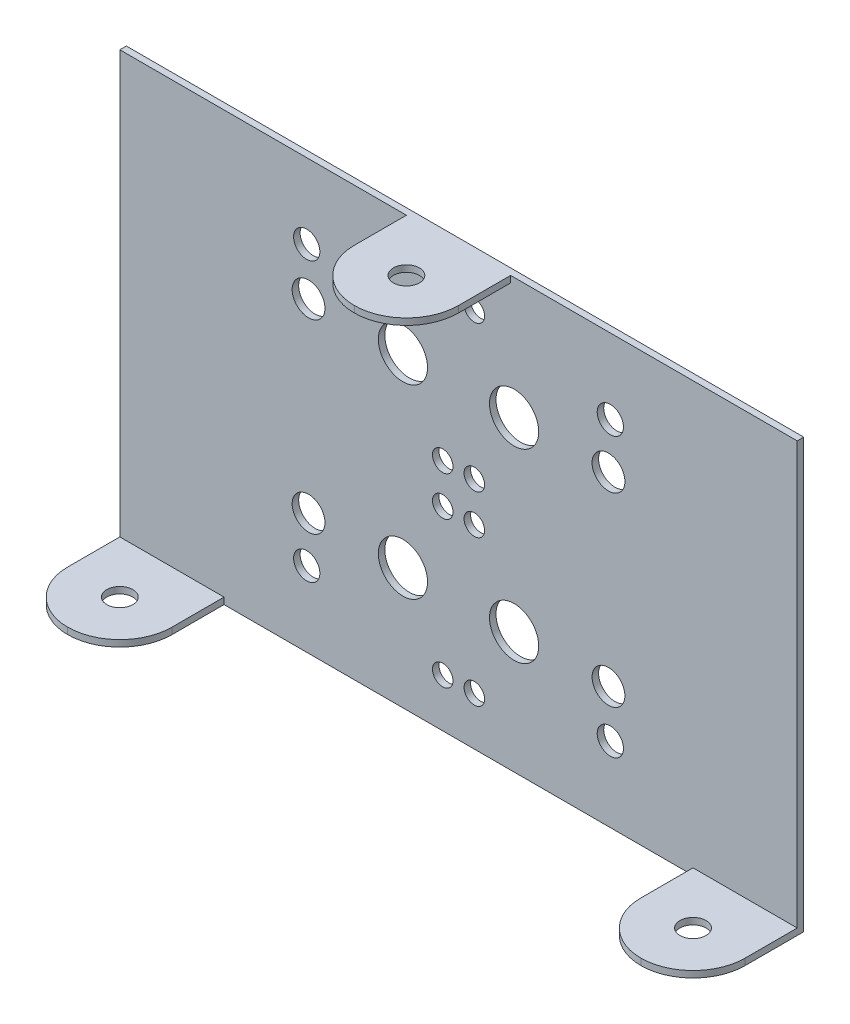
SolidWorks part; units mm, degrees
ref_plane "Front Plane" through (0, 0, 0) normal (0, 0, 1) x (1, 0, 0)
ref_plane "Top Plane" through (0, 0, 0) normal (0, 1, 0) x (1, 0, 0)
ref_plane "Right Plane" through (0, 0, 0) normal (1, 0, 0) x (0, 0, -1)
sketch "Sketch1" plane through (0, 0, 0) normal (0, 1, 0) x (1, 0, 0)
  line L0 (0, 0) -> (-69.85, 0)
  line L1 (-69.85, 0) -> (-69.85, 12.7)
  line L2 (-69.85, 12.7) -> (0, 12.7)
  line L3 (0, 12.7) -> (0, 0)
  line L4 (-69.85, 6.35) -> (-63.5, 6.35)
  line L5 (-34.925, 0) -> (-34.925, 12.7)
  line L6 (-63.5, 6.35) -> (-57.15, 6.35)
  line L7 (-57.15, 6.35) -> (-57.15, 12.7)
  line L8 (-57.15, 6.35) -> (-57.15, 0)
  line L9 (-12.7, 6.35) -> (-12.7, 0)
  line L10 (-12.7, 6.35) -> (-12.7, 12.7)
  line L11 (-6.35, 6.35) -> (-12.7, 6.35)
  circle A0 centre (-63.5, 6.35) radius 1.5875
  circle A1 centre (-6.35, 6.35) radius 1.5875
  dimension "D4" = 3.175
  dimension "D1" = 69.85
  dimension "D2" = 12.7
  dimension "D3" = 6.35
  dimension "D5" = 34.925
  dimension "D6" = 34.925
  dimension "D7" = 12.7
  dimension "D8" = 12.7
extrude "Boss-Extrude1" add sketch "Sketch1" along normal blind 1.5875 contours A0 L4 L1 L0 L8 L6 | A0 L6 L7 L2 L1 L4 | A1 L9 L0 L3 L2 L10 region at (-6.35, 0, -0.1796) region at (-63.5, 0, -3.0459) region at (-63.5, 0, -9.6541)
sketch "Sketch2" plane through (0, 0, -12.7) normal (0, 0, -1) x (-1, 0, 0)
  line L1 (0, 0) -> (69.85, 0)
  line L2 (0, 0) -> (0, 53)
  line L3 (0, 53) -> (69.85, 53)
  line L4 (69.85, 0) -> (69.85, 53)
  dimension "D1" = 69.85
  dimension "D2" = 53
extrude "Boss-Extrude2" add sketch "Sketch2" along normal blind 1.5875
sketch "Sketch3" plane through (0, 0, -14.2875) normal (0, 0, -1) x (-1, 0, 0)
  line L0 (-27.8972, 15.9448) -> (-27.8972, 27.4448)
  line L1 (-27.8972, 38.6448) -> (-27.8972, 27.4448)
  line L2 (-39.2472, 38.6448) -> (-16.5472, 38.6448)
  line L3 (-39.2472, 38.6448) -> (-39.2472, -3.3552)
  line L4 (-39.2472, -3.3552) -> (-16.5472, -3.3552)
  line L5 (-16.5472, 38.6448) -> (-16.5472, -3.3552)
  line L6 (-36.7972, 36.1448) -> (-18.9972, 36.1448)
  line L7 (-39.2472, 38.6448) -> (-36.7972, 38.6448)
  line L8 (-39.2472, 38.6448) -> (-39.2472, 36.1448)
  line L9 (-39.2472, 36.1448) -> (-36.7972, 36.1448)
  line L10 (-36.7972, 38.6448) -> (-36.7972, 36.1448)
  circle A0 centre (-27.8972, 15.9448) radius 2
  circle A1 centre (-27.8972, 27.4448) radius 3
  circle A2 centre (-36.7972, 36.1448) radius 1.25
  circle A3 centre (-18.9972, 36.1448) radius 1.25
  dimension "D1" = 4
  dimension "D5" = 6
  dimension "D7" = 11.2
  dimension "D11" = 2.5
  dimension "D13" = 2.5
  dimension "D2" = 42
  dimension "D3" = 22.7
  dimension "D4" = 11.5
  dimension "D6" = 11.2
  dimension "D8" = 11.5
  dimension "D9" = 2.5
  dimension "D10" = 2.45
  dimension "D12" = 2.45
sketch "Sketch4" plane through (0, 0, -14.2875) normal (0, 0, -1) x (-1, 0, 0)
  line L0 (0, 0) -> (69.85, 0)
  line L1 (0, 0) -> (69.85, 0) construction
  line L6 (98.3204, -4.2413) -> (56.3204, -4.2413)
  line L9 (56.3204, -26.9413) -> (56.3204, -4.2413)
  line L10 (98.3204, -26.9413) -> (56.3204, -26.9413)
  line L13 (98.3204, -26.9413) -> (98.3204, -4.2413)
  circle A4 centre (95.8204, -6.6913) radius 1.25
  circle A5 centre (95.8204, -24.4913) radius 1.25
  circle A6 centre (87.1204, -15.5913) radius 3
  circle A7 centre (75.6204, -15.5913) radius 2
  dimension "D1" = 69.85
sketch "Sketch5" plane through (0, 1.5875, 0) normal (0, 1, 0) x (1, 0, 0)
  line L0 (-6.35, 6.35) -> (-76.2, 6.35)
  line L1 (-69.85, 0) -> (-82.55, 0)
  line L2 (-69.85, 6.35) -> (-82.55, 6.35)
  line L3 (-76.2, 6.35) -> (-76.2, 12.7)
  line L4 (-69.85, 12.7) -> (-82.55, 12.7)
  line L5 (-82.55, 0) -> (-82.55, 12.7)
  line L6 (-69.85, 0) -> (-69.85, 12.7)
  circle A0 centre (-76.2, 6.35) radius 1.5875
  point P12 (-76.2, 0)
  line M3 (-69.85, 12.7) -> (-69.85, 0)
  dimension "D1" = 3.175
  dimension "D2" = 69.85
  dimension "D3" = 6.35
  dimension "D4" = 6.35
extrude "Boss-Extrude3" add sketch "Sketch5" against normal blind 1.5875 contours A0 L2 L5 L1 L0 M3 | A0 L3 L4 L5 L2 | A0 L0 L4 L3 M3 region at (-76.2, 1.5875, -3.0459) region at (-72.8959, 1.5875, -9.6541) region at (-79.5041, 1.5875, -9.6541)
sketch "Sketch6" plane through (-69.85, 0, 0) normal (-1, 0, 0) x (0, 0, 1)
  line L1 (-14.2875, 53) -> (-12.7, 53)
  line L2 (-14.2875, 53) -> (-14.2875, 0)
  line L3 (-14.2875, 0) -> (-12.7, 0)
  line L4 (-12.7, 53) -> (-12.7, 0)
extrude "Boss-Extrude4" add sketch "Sketch6" along normal blind 12.7
sketch "Sketch7" plane through (0, 1.5875, 0) normal (0, 1, 0) x (1, 0, 0)
  line L1 (-57.15, 0) -> (-69.85, 0)
  line L2 (-57.15, 0) -> (-57.15, 12.7)
  line L3 (-57.15, 12.7) -> (-69.85, 12.7)
  line L4 (-69.85, 0) -> (-69.85, 12.7)
extrude "Cut-Extrude1" cut sketch "Sketch7" against normal blind 12.7
sketch "Sketch10" plane through (0, 0, 0) normal (1, 0, 0) x (0, 0, -1)
  line L0 (0, 0) -> (0, 0.7937)
  line L1 (0, 1.5875) -> (0, 0) construction
  line L2 (0, 0.7937) -> (13.4937, 0.7938)
  line L3 (13.4937, 53) -> (13.4937, -1.4744)
  line L4 (14.2875, 53) -> (12.7, 53) construction
  line L5 (0, 0) -> (14.2875, 0)
  line L6 (14.2875, 0) -> (14.2875, 53)
  line L7 (14.2875, 53) -> (13.4937, 53)
  line M3 (0, 1.5875) -> (0, 0)
  line M4 (0, 0) -> (14.2875, 0)
  line M5 (14.2875, 0) -> (14.2875, 53)
  line M6 (14.2875, 53) -> (12.7, 53)
extrude "Cut-Extrude3" cut sketch "Sketch10" against normal through all contours L3 L2 M3 M4 | L3 M6 M4 M5 region at (0, 0.3969, -6.7469) region at (0, 26.5, -13.8906)
sketch "Sketch13" plane through (0, 0, -13.4937) normal (0, 0, -1) x (-1, 0, 0)
  line L0 (0, 0.7938) -> (23, 0.7938)
  line L1 (0, 53) -> (41.275, 53)
  line L2 (82.55, 53) -> (0, 53) construction
  line L3 (41.275, 53) -> (41.275, 0.7938)
  line L4 (41.275, 26.8969) -> (19.6299, 26.8969)
  line L5 (82.55, 0.7938) -> (0, 0.7938) construction
  line L6 (23, 0.7938) -> (23, 15.5875)
  circle A0 centre (43.2, 24.4875) radius 1.25
  circle A1 centre (43.2, 6.6875) radius 1.25
  circle A2 centre (34.5, 15.5875) radius 3
  circle A3 centre (23, 15.5875) radius 2
  circle A4 centre (39.35, 6.6875) radius 1.25
  circle A5 centre (39.35, 24.4875) radius 1.25
  circle A6 centre (48.05, 15.5875) radius 3
  circle A7 centre (59.55, 15.5875) radius 2
  circle A8 centre (59.55, 38.2063) radius 2
  circle A9 centre (48.05, 38.2063) radius 3
  circle A10 centre (39.35, 29.3063) radius 1.25
  circle A11 centre (39.35, 47.1063) radius 1.25
  circle A12 centre (23, 38.2063) radius 2
  circle A13 centre (34.5, 38.2063) radius 3
  circle A14 centre (43.2, 47.1063) radius 1.25
  circle A15 centre (43.2, 29.3063) radius 1.25
  dimension "D1" = 23
  dimension "D2" = 14.7937
extrude "Cut-Extrude4" cut sketch "Sketch13" against normal blind 12.7 contours A3 | A2 | A12 | A13 | A9 | A8 | A6 | A7 | A4 | A1 | A14 | A10 | A5 | A0 | A15 | A11 region at (-43.2, 24.4875, -13.4937) region at (-43.2, 6.6875, -13.4937) region at (-34.5, 15.5875, -13.4937) region at (-24.3742, 14.2133, -13.4937) region at (-39.35, 6.6875, -13.4937) region at (-39.35, 24.4875, -13.4937) region at (-48.05, 15.5875, -13.4937) region at (-59.55, 15.5875, -13.4937) region at (-59.55, 38.2063, -13.4937) region at (-48.05, 38.2063, -13.4937) region at (-39.35, 29.3063, -13.4937) region at (-23, 38.2063, -13.4937) region at (-34.5, 38.2063, -13.4937) region at (-43.2, 47.1063, -13.4937) region at (-43.2, 29.3063, -13.4937)
fillet "Fillet1" radius 6.35 2 edges at (-12.7, 1.1906, 0) (0, 1.1906, 0)
fillet "Fillet2" radius 6.35 2 edges at (-82.55, 1.1906, 0) (-69.85, 1.1906, 0)
sketch "Sketch14" plane through (0, 53, 0) normal (0, 1, 0) x (1, 0, 0)
  line L1 (-82.55, 12.7) -> (0, 12.7) construction
  line L2 (-34.925, 0) -> (-34.925, 12.7)
  line L3 (-47.625, 0) -> (-47.625, 12.7)
  line L4 (-47.625, 12.7) -> (-34.925, 12.7)
  line L5 (-47.625, 0) -> (-34.925, 0)
  circle A0 centre (-41.275, 6.35) radius 1.5875
  dimension "D2" = 3.175
extrude "Boss-Extrude5" add sketch "Sketch14" against normal blind 0.7937
fillet "Fillet3" radius 6.35 2 edges at (-47.625, 52.6031, 0) (-34.925, 52.6031, 0)
sketch "Sketch15" plane through (0, 0, -13.4937) normal (0, 0, -1) x (-1, 0, 0)
  line L1 (41.275, 53) -> (41.275, 0.7938)
  line L2 (82.55, 0.7938) -> (0, 0.7938) construction
  line L3 (0, 26.8969) -> (82.55, 26.8969)
  line L4 (0, 53) -> (0, 0.7938) construction
  line L5 (82.55, 53) -> (82.55, 0.7938) construction
  line L6 (41.275, 23.862) -> (41.275, 63.862)
  circle A0 centre (22.775, 43.862) radius 1.6
  circle A1 centre (59.775, 43.862) radius 1.6
  circle A2 centre (59.775, 9.9317) radius 1.6
  circle A3 centre (22.775, 9.9317) radius 1.6
  point P18 (41.275, 43.862)
  dimension "D1" = 3.2
  dimension "D3" = 3.2
  dimension "D2" = 37
extrude "Cut-Extrude7" cut sketch "Sketch15" against normal blind 0.7937 contours A0 | A3 | A2 | A1 region at (-22.775, 43.862, -13.4937) region at (-59.775, 43.862, -13.4937) region at (-59.775, 9.9317, -13.4937) region at (-22.775, 9.9317, -13.4937)
